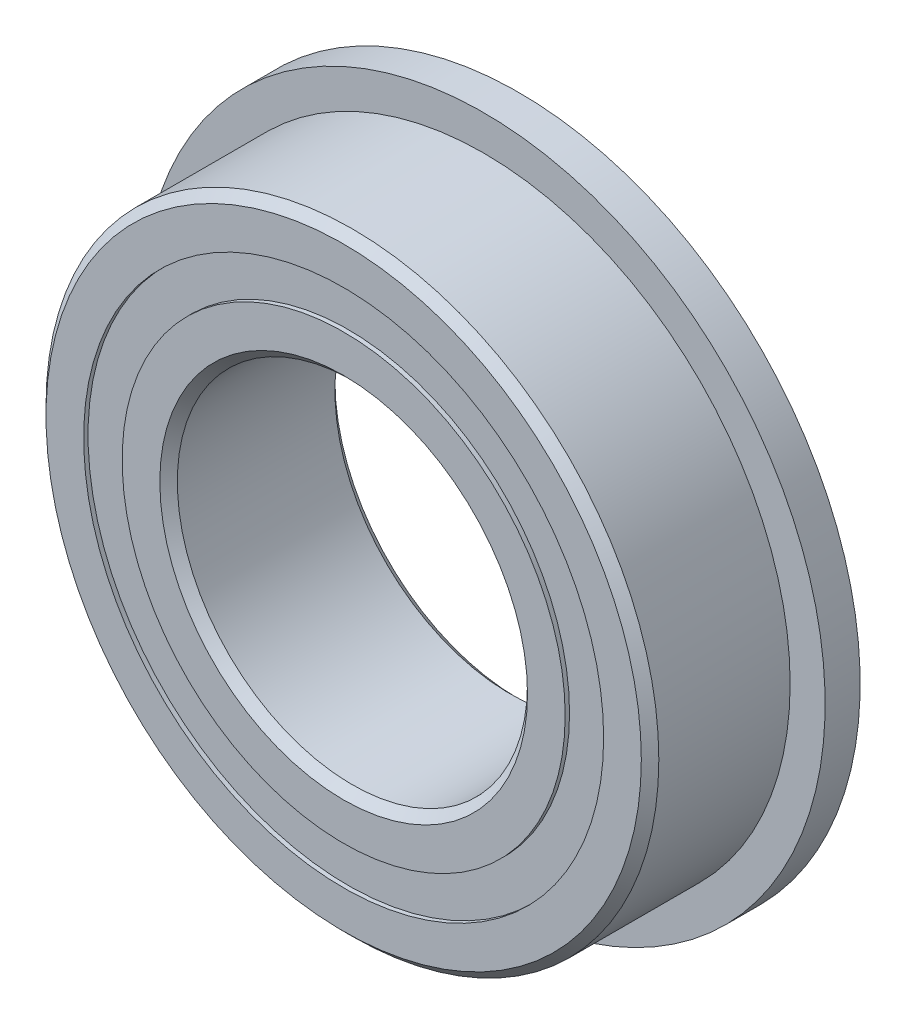
SolidWorks part; units mm, degrees
material "Alloy Steel (SS)"
ref_plane "Front Plane" through (0, 0, 0) normal (0, 0, 1) x (1, 0, 0)
ref_plane "Top Plane" through (0, 0, 0) normal (0, 1, 0) x (1, 0, 0)
ref_plane "Right Plane" through (0, 0, 0) normal (1, 0, 0) x (0, 0, -1)
sketch "Sketch1" plane through (0, 0, 0) normal (1, 0, 0) x (0, 0, -1)
  line L0 (-2, 0) -> (2, 0) construction
  line L1 (0, 7) -> (0, -7) construction
  line L2 (1.8, 7) -> (-1.8, 7)
  line L3 (-1.8, 7) -> (-2, 6.8)
  line L4 (-2, 6.8) -> (-2, 5.9396)
  line L5 (-2, 5.9396) -> (-0.8889, 5.9396)
  line L6 (2, 5.9396) -> (0.8889, 5.9396)
  line L7 (2, 6.8) -> (2, 5.9396)
  line L8 (1.8, 7) -> (2, 6.8)
  line L9 (0, 7) -> (0, 5.5) construction
  line L10 (0, 5.5) -> (0, 4) construction
  arc A0 (-0.8889, 5.9396) -> (0.8889, 5.9396) centre (0, 5.5) cw
  point P14 (0, 4)
  dimension "Width" = 4
  dimension "OD" = 14
  dimension "D1" = 45
  dimension "D2" = 0.2
  dimension "Shaft Dia" = 8
  dimension "D3" = 1.7778
  dimension "D4" = 0.4396
revolve "Revolve1" add sketch "Sketch1" angle 360 about L0
sketch "Sketch3" plane through (0, 0, 0) normal (1, 0, 0) x (0, 0, -1)
  line L0 (-2, 5.0604) -> (-0.8889, 5.0604)
  line L1 (0, 7) -> (0, -7) construction
  line L2 (-2, 6.8) -> (-2, 5.9396) construction
  line L3 (-2, 5.0604) -> (-2, 4.2)
  line L4 (-1.8, 7) -> (-2, 6.8) construction
  line L5 (-2, 4.2) -> (-1.8, 4)
  line L6 (-1.8, 4) -> (1.8, 4)
  line L7 (1.8, 7) -> (1.8, -7) construction
  line L8 (1.8, 4) -> (2, 4.2)
  line L9 (2, -6.8) -> (2, 6.8) construction
  line L10 (2, 4.2) -> (2, 5.0604)
  line L11 (2, 5.0604) -> (0.8889, 5.0604)
  line L13 (1.8, 7) -> (2, 6.8) construction
  arc A0 (0.8889, 5.9396) -> (-0.8889, 5.9396) centre (0, 5.5) ccw construction
  arc A1 (0.8889, 5.0604) -> (-0.8889, 5.0604) centre (0, 5.5) cw
revolve "Revolve3" add sketch "Sketch3" angle 360 about L0
sketch "Sketch4" plane through (0, 0, 0) normal (1, 0, 0) x (0, 0, -1)
  line L0 (-0.9916, 5.5) -> (0.9916, 5.5)
  arc A2 (-0.9916, 5.5) -> (0.9916, 5.5) centre (0, 5.5) cw
  arc A3 (0.8889, 5.9396) -> (-0.8889, 5.9396) centre (0, 5.5) ccw construction
revolve "Revolve4" add sketch "Sketch4" angle 360 about L0
ref_axis "Axis1" through (0, 0, -2) along (0, 0, 1)
pattern_circular "CirPattern1" count 12 every 30 about axis through (0, 0, -2) along (0, 0, 1) of bodies 104
sketch "Sketch5" plane through (0, 0, 0) normal (1, 0, 0) x (0, 0, -1)
  line L0 (-2, 5.9396) -> (-0.8889, 5.9396) construction
  line L1 (-1.9, 5.9396) -> (-0.9916, 5.9396)
  line L2 (-1.9, 5.9396) -> (-1.9, 5.0604)
  line L3 (-1.9, 5.0604) -> (-0.9916, 5.0604)
  line L4 (-0.9916, 5.9396) -> (-0.9916, 5.0604)
  line L5 (-2, 5.0604) -> (-0.8889, 5.0604) construction
  line L6 (2, 5.9396) -> (0.8889, 5.9396) construction
  line L7 (1.9, 5.9396) -> (0.9916, 5.9396)
  line L8 (1.9, 5.9396) -> (1.9, 5.0604)
  line L9 (1.9, 5.0604) -> (0.9916, 5.0604)
  line L10 (0.9916, 5.9396) -> (0.9916, 5.0604)
  line L11 (2, 5.0604) -> (0.8889, 5.0604) construction
  line L12 (-1.8, 7) -> (-2, 6.8) construction
  point P18 (-1.9, 6.9)
revolve "Revolve5" add sketch "Sketch5" angle 360 about L0
sketch "Sketch6" plane through (0, 0, 0) normal (1, 0, 0) x (0, 0, -1)
  line L0 (2, 0) -> (-2, 0) construction
  line L1 (2, 5.9396) -> (1.2, 5.9396)
  line L2 (2, 5.9396) -> (2, 7.8)
  line L3 (2, 7.8) -> (1.2, 7.8)
  line L4 (1.2, 5.9396) -> (1.2, 7.8)
  dimension "Th" = 0.8
  dimension "Flange OD" = 15.6
revolve "Revolve6" add sketch "Sketch6" angle 360 about L0
equation "\"D2@Sketch1\" = \"Width@Sketch1\"*.05"
equation "\"D3@Sketch1\" = \"Width@Sketch1\"/2.25"
equation "\"D4@Sketch1\" = (((\"OD@Sketch1\"-\"Width@Sketch1\")/2)/3.25)/3.5"
equation "\"D2@CirPattern1\" = 360/\"Balls@CirPattern1\""
